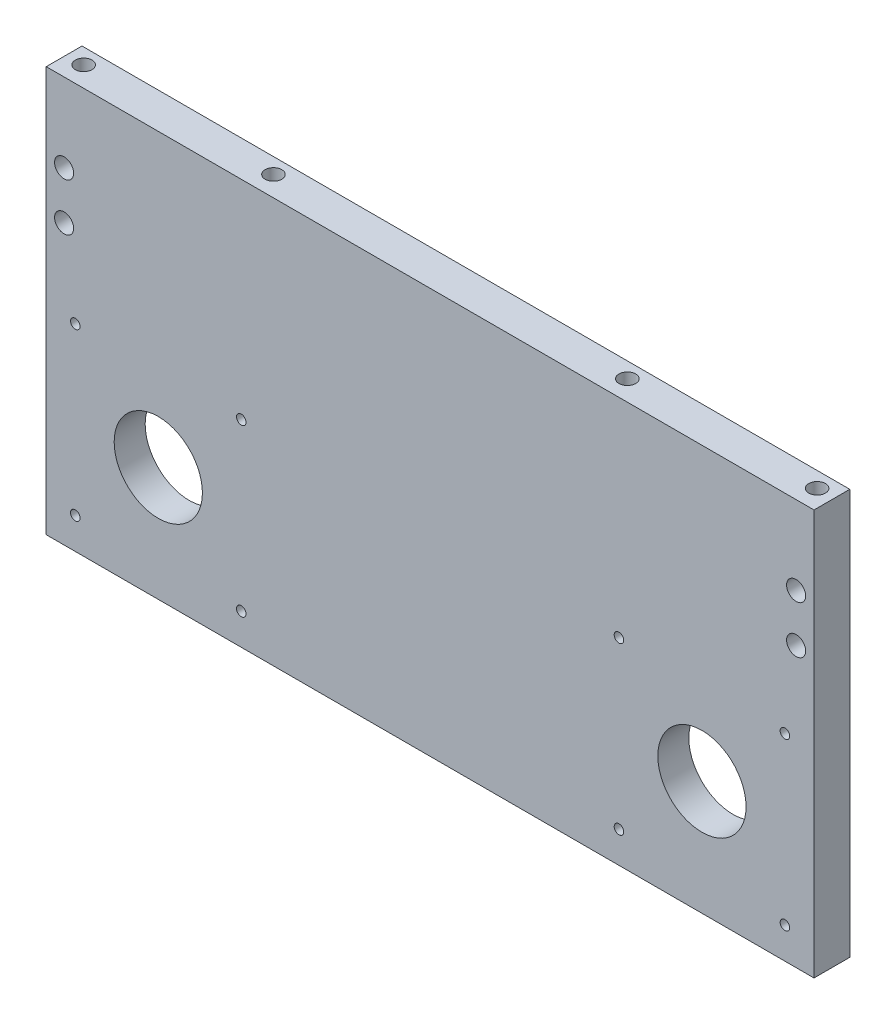
SolidWorks part; units mm, degrees
ref_plane "Płaszczyzna przednia" through (0, 0, 0) normal (0, 0, 1) x (1, 0, 0)
ref_plane "Płaszczyzna górna" through (0, 0, 0) normal (0, 1, 0) x (1, 0, 0)
ref_plane "Płaszczyzna prawa" through (0, 0, 0) normal (1, 0, 0) x (0, 0, -1)
sketch "Szkic1" plane through (0, 0, 0) normal (0, 0, 1) x (1, 0, 0)
  line L1 (161, -85) -> (-161, -85)
  line L2 (161, -85) -> (161, 85)
  line L3 (161, 85) -> (-161, 85)
  line L4 (-161, -85) -> (-161, 85)
  line L5 (161, -85) -> (-161, 85) construction
  line L6 (161, 85) -> (-161, -85) construction
  point P0 (0, 0)
  dimension "D1" = 322
  dimension "D2" = 170
extrude "Dodanie-wyciągnięcie1" add sketch "Szkic1" along normal blind 15
sketch "Szkic2" plane through (0, 0, 15) normal (0, 0, 1) x (1, 0, 0)
  line L2 (-161, -85) -> (161, -85) construction
  line L7 (-161, 85) -> (-161, -85) construction
  circle A1 centre (-148.8, -71.87) radius 2
  dimension "D1" = 13.13
  dimension "D2" = 12.2
  dimension "D5" = 4
extrude "Wytnij-wyciągnięcie2" cut sketch "Szkic2" against normal blind 17.75 contours A1 region at (-148.8, -71.87, 15)
pattern_linear "Szyk liniowy1" count 2 spacing 69.6 along (1, 0, 0) count 2 spacing 69.6 along (0, 1, 0) of "Wytnij-wyciągnięcie2"
sketch "Szkic5" plane through (0, 0, 0) normal (0, 0, -1) x (-1, 0, 0)
  line L1 (161, -85) -> (-161, -85) construction
  line L2 (161, 85) -> (161, -85) construction
  circle A1 centre (114, -37.07) radius 37.5
  dimension "D1" = 47.93
  dimension "D5" = 75
  dimension "D2" = 47
extrude "Wytnij-wyciągnięcie3" cut sketch "Szkic5" against normal blind 2 contours A1 region at (-114, -37.07, 0)
sketch "Szkic7" plane through (0, 0, 2) normal (0, 0, -1) x (-1, 0, 0)
  circle A3 centre (114, -37.07) radius 18.5
  dimension "D1" = 37
extrude "Wytnij-wyciągnięcie4" cut sketch "Szkic7" against normal blind 17.75 contours A3 region at (-114, -37.07, 2)
pattern_linear "Szyk liniowy2" count 2 spacing 228 along (1, 0, 0) of "Wytnij-wyciągnięcie2", "Szyk liniowy1", "Wytnij-wyciągnięcie3", "Wytnij-wyciągnięcie4"
sketch "Szkic8" plane through (0, 85, 0) normal (0, 1, 0) x (1, 0, 0)
  line L0 (-161, -15) -> (-161, 0) construction
  line L1 (161, -15) -> (-161, -15) construction
  line L2 (161, -15) -> (161, 0) construction
  line L3 (161, -15) -> (-161, -15) construction
  circle A0 centre (-153.8, -6.5) radius 4
  circle A1 centre (153.8, -6.5) radius 4
  dimension "D1" = 7.2
  dimension "D3" = 8
  dimension "D6" = 8
  dimension "D2" = 8.5
  dimension "D4" = 7.2
  dimension "D5" = 8.5
extrude "Wytnij-wyciągnięcie5" [suppressed] cut sketch "Szkic8" against normal blind 20
sketch "Szkic10" plane through (0, 0, 15) normal (0, 0, 1) x (1, 0, 0)
  line L0 (161, 85) -> (-161, 85) construction
  line L1 (-161, 85) -> (-161, -85) construction
  circle A0 centre (-153.5, 52) radius 4
  circle A1 centre (-153.5, 32) radius 4
  dimension "D1" = 53
  dimension "D3" = 8
  dimension "D4" = 8
  dimension "D2" = 20
  dimension "D5" = 7.5
extrude "Wytnij-wyciągnięcie7" cut sketch "Szkic10" against normal through all
sketch "Szkic11" plane through (0, 0, 15) normal (0, 0, 1) x (1, 0, 0)
  line L0 (161, 85) -> (-161, 85) construction
  line L1 (161, -85) -> (161, 85) construction
  circle A0 centre (153.5, 32) radius 4
  circle A1 centre (153.5, 52) radius 4
  dimension "D1" = 53
  dimension "D2" = 8
  dimension "D3" = 8
  dimension "D4" = 7.5
  dimension "D5" = 20
extrude "Wytnij-wyciągnięcie8" cut sketch "Szkic11" against normal through all
hole_wizard "Otwór gwintowany M8x1.01" positions "Szkic12" profile "Szkic13" tap size "M8x1.0" standard "Ansi Metric"
sketch "Szkic12" plane through (0, 85, 0) normal (0, 1, 0) x (1, 0, 0)
  line L0 (-161, -6.5) -> (161, -6.5) construction
  line L1 (-161, -15) -> (-161, 0) construction
  line L2 (161, -15) -> (161, 0) construction
  line L5 (161, -15) -> (-161, -15) construction
  point P0 (-153.8, -6.5)
  point P2 (-74.2, -6.5)
  point P4 (74.2, -6.5)
  point P6 (153.8, -6.5)
  point P19 (0, 0)
  point P20 (0, 0)
  point P23 (0, 0)
  point P24 (0, 0)
  point P25 (0, 0)
  point P26 (0, 0)
  dimension "D1" = 8.5
  dimension "D2" = 7.2
  dimension "D3" = 7.2
  dimension "D4" = 79.6
  dimension "D5" = 79.6
sketch "Szkic13" plane through (-153.8, 85, 6.5) normal (1, 0, 0) x (0, 0, 1)
  line L0 (0, 0) -> (0, 23.103)
  line L1 (0, 23.103) -> (3.5, 21)
  line L2 (3.5, 21) -> (3.5, 0)
  line L5 (3.5, 0) -> (0, 0)
  line L10 (0, 23.103) -> (-3.5, 21) construction
  line L11 (0, -6.35) -> (0, 107.95) construction
  dimension "Średnica wiertła gwintu" = 7
  dimension "Głębokość otworu gwintowanego" = 21
  dimension "Kąt wiertła" = 118
cosmetic thread "Gwint otworu1" parameters "D1"=16, "D2"=8
cosmetic thread "Gwint otworu2" parameters "D1"=16, "D2"=8
cosmetic thread "Gwint otworu3" parameters "D1"=16, "D2"=8
cosmetic thread "Gwint otworu4" parameters "D1"=16, "D2"=8
